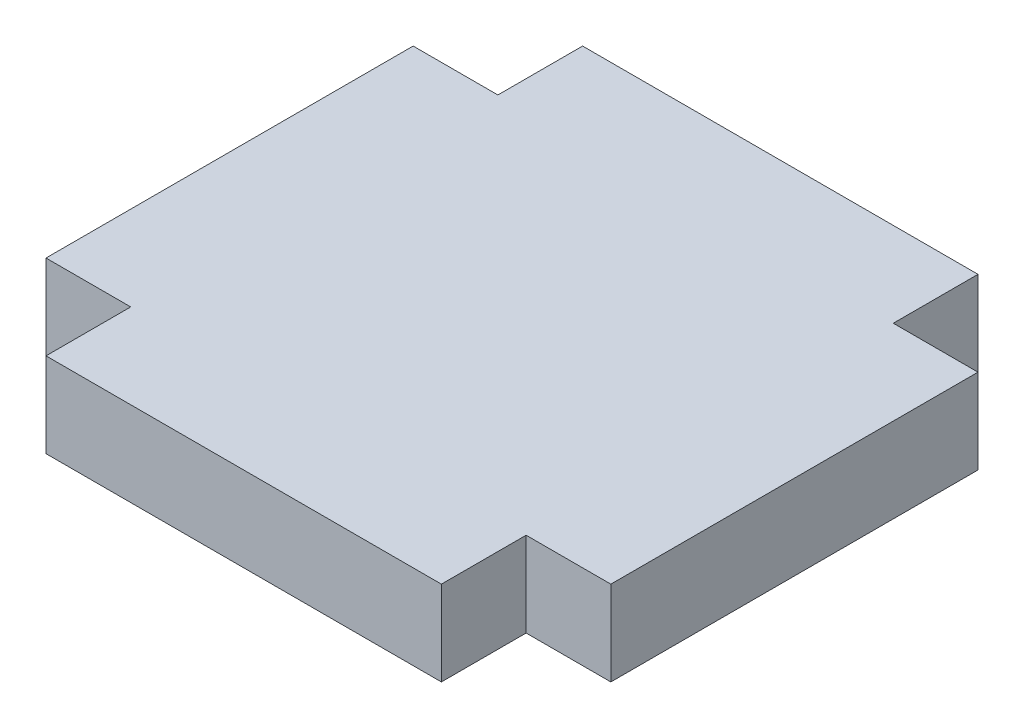
SolidWorks part; units mm, degrees
ref_plane "Alzado" through (0, 0, 0) normal (0, 0, 1) x (1, 0, 0)
ref_plane "Planta" through (0, 0, 0) normal (0, 1, 0) x (1, 0, 0)
ref_plane "Vista lateral" through (0, 0, 0) normal (1, 0, 0) x (0, 0, -1)
sketch "Croquis1" plane through (0, 0, 0) normal (0, 1, 0) x (1, 0, 0)
  line L0 (0, 0) -> (0, 13)
  line L1 (0, 13) -> (3, 13)
  line L2 (20, 13) -> (20, 0)
  line L3 (20, 0) -> (17, 0)
  line L4 (3, 0) -> (0, 0)
  line L5 (3, 16) -> (17, 16)
  line L6 (17, 16) -> (17, 13)
  line L7 (3, 16) -> (3, 13)
  line L9 (3, -3) -> (3, 0)
  line L10 (17, -3) -> (17, 0)
  line L11 (3, -3) -> (17, -3)
  line L13 (17, 13) -> (20, 13)
  dimension "D1" = 13
  dimension "D2" = 20
extrude "Saliente-Extruir1" add sketch "Croquis1" along normal blind 3
